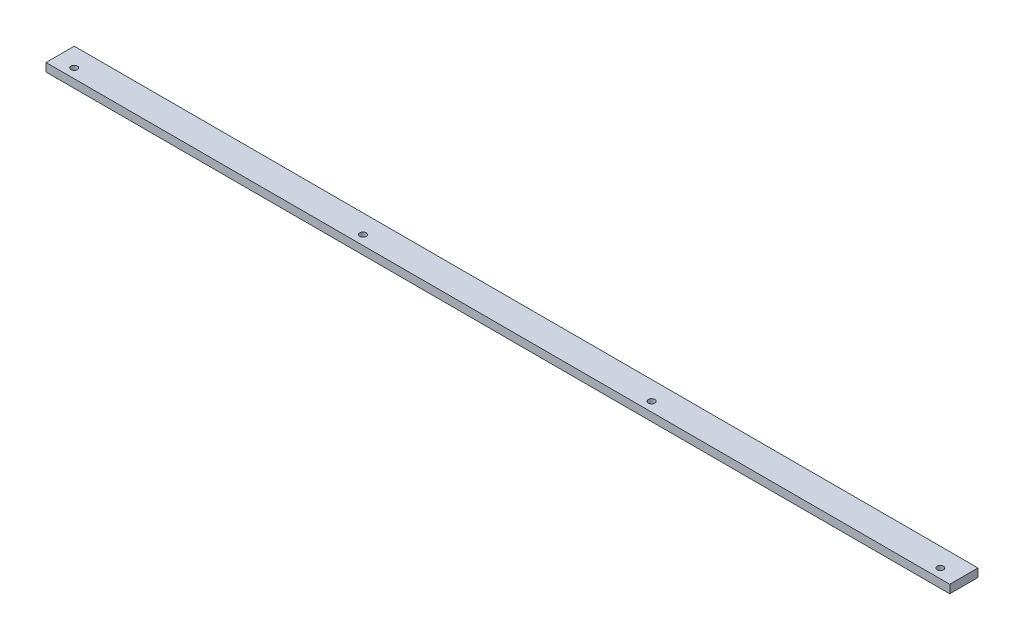
SolidWorks part; units mm, degrees
material "Rubber"
ref_plane "Front" through (0, 0, 0) normal (0, 0, 1) x (1, 0, 0)
ref_plane "Top" through (0, 0, 0) normal (0, 1, 0) x (1, 0, 0)
ref_plane "Right" through (0, 0, 0) normal (1, 0, 0) x (0, 0, -1)
sketch "Sketch1" plane through (0, 0, 0) normal (0, 1, 0) x (1, 0, 0)
  line L1 (-304.8, 9.525) -> (304.8, 9.525)
  line L2 (-304.8, 9.525) -> (-304.8, -9.525)
  line L3 (-304.8, -9.525) -> (304.8, -9.525)
  line L4 (304.8, 9.525) -> (304.8, -9.525)
  line L5 (-304.8, 9.525) -> (304.8, -9.525) construction
  line L6 (-304.8, -9.525) -> (304.8, 9.525) construction
  point P0 (0, 0)
  dimension "D1" = 19.05
  dimension "D2" = 609.6
extrude "Boss-Extrude1" add sketch "Sketch1" along normal blind 5.588
hole_wizard "#8 Clearance Hole1" positions "Sketch2" profile "Sketch3" hole size "#8" standard "ANSI Inch" end condition through all
sketch "Sketch2" plane through (0, 0, 0) normal (0, -1, 0) x (-1, 0, 0)
  point P0 (-292.1, -3.175)
  point P3 (-97.3667, -3.175)
  point P6 (97.3667, -3.175)
  point P9 (292.1, -3.175)
sketch "Sketch3" plane through (292.1, 0, 3.175) normal (1, 0, 0) x (0, 0, -1)
  line L0 (0, 0) -> (0, 5.588)
  line L1 (0, 5.588) -> (2.1526, 5.588)
  line L2 (2.1526, 5.588) -> (2.1526, 0)
  line L5 (2.1526, 0) -> (0, 0)
  line L11 (0, -6.35) -> (0, 107.95) construction
  dimension "Thru Hole Dia." = 4.3053
  dimension "Thru Hole Depth" = 5.588
